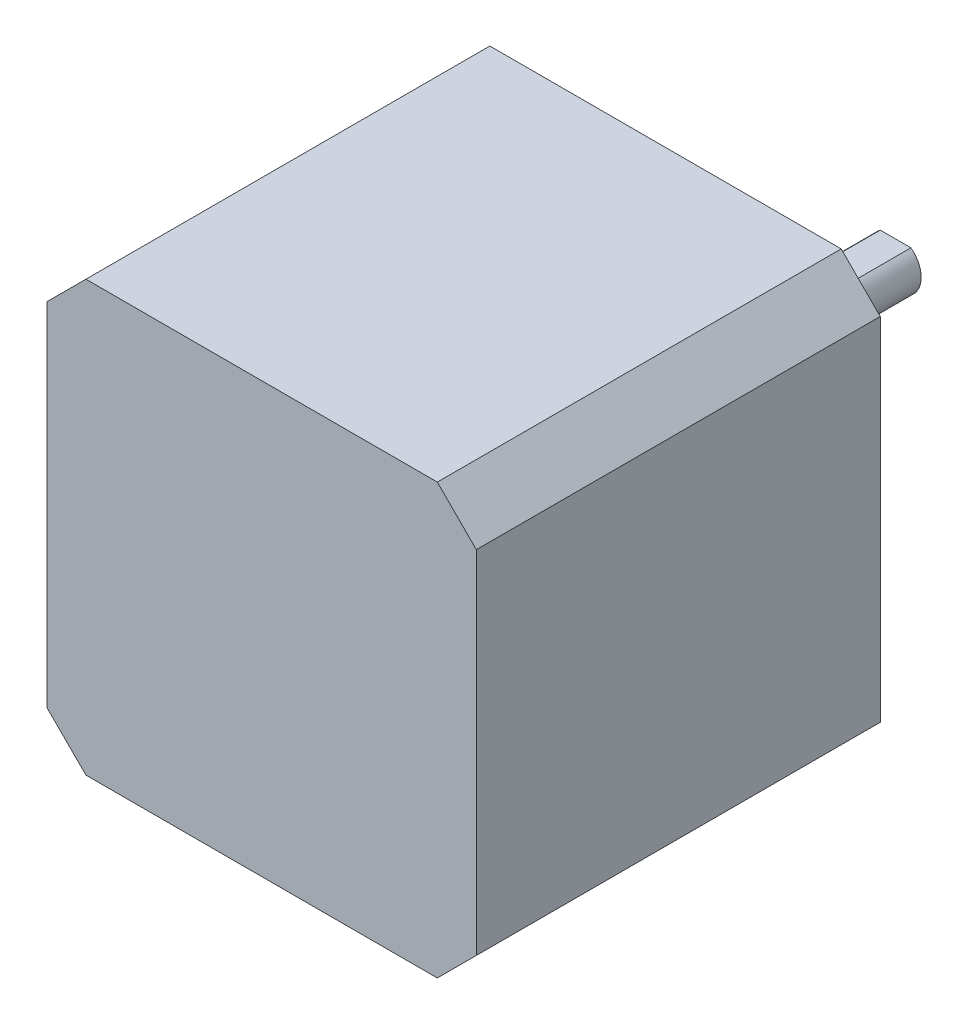
SolidWorks part; units mm, degrees
ref_plane "前视基准面" through (0, 0, 0) normal (0, 0, 1) x (1, 0, 0)
ref_plane "上视基准面" through (0, 0, 0) normal (0, 1, 0) x (1, 0, 0)
ref_plane "右视基准面" through (0, 0, 0) normal (1, 0, 0) x (0, 0, -1)
sketch "草图1" plane through (0, 0, 0) normal (0, 0, 1) x (1, 0, 0)
  line L3 (-17.1838, 21) -> (17.1838, 21)
  line L6 (21, 17.1838) -> (17.1838, 21)
  line L7 (-21, 17.1838) -> (-17.1838, 21)
  line L9 (-17.1838, -21) -> (-21, -17.1838)
  line L10 (-21, 17.1838) -> (-21, -17.1838)
  line L11 (17.1838, -21) -> (-17.1838, -21)
  line L12 (17.1838, -21) -> (21, -17.1838)
  line L13 (21, -17.1838) -> (21, 17.1838)
  point P0 (0, 0)
extrude "凸台-拉伸1" add sketch "草图1" along normal blind 39.5
sketch "草图2" plane through (0, 0, 0) normal (0, 0, -1) x (-1, 0, 0)
  circle A0 centre (0, 0) radius 11
extrude "凸台-拉伸2" add sketch "草图2" along normal blind 2
sketch "草图3" plane through (0, 0, -2) normal (0, 0, -1) x (-1, 0, 0)
  circle A0 centre (0, 0) radius 2.5
extrude "凸台-拉伸3" add sketch "草图3" along normal blind 20.5
sketch "草图4" plane through (0, 0, 0) normal (0, 0, -1) x (-1, 0, 0)
  circle A0 centre (-15.5, -15.5) radius 1.5
  circle A1 centre (-15.5, 15.5) radius 1.5
  circle A2 centre (15.5, 15.5) radius 1.5
  circle A3 centre (15.5, -15.5) radius 1.5
  point P0 (0, 0)
  point P16 (0, 0)
  dimension "D1" = 4
extrude "切除-拉伸1" cut sketch "草图4" against normal blind 5
sketch "草图5" plane through (0, 0, -22.5) normal (0, 0, -1) x (-1, 0, 0)
  line L2 (1.5, 2) -> (-1.5, 2)
  circle A0 centre (0, 0) radius 2.5 construction
  arc A2 (1.5, 2) -> (-1.5, 2) centre (0, 0) ccw
extrude "切除-拉伸2" cut sketch "草图5" against normal blind 18
